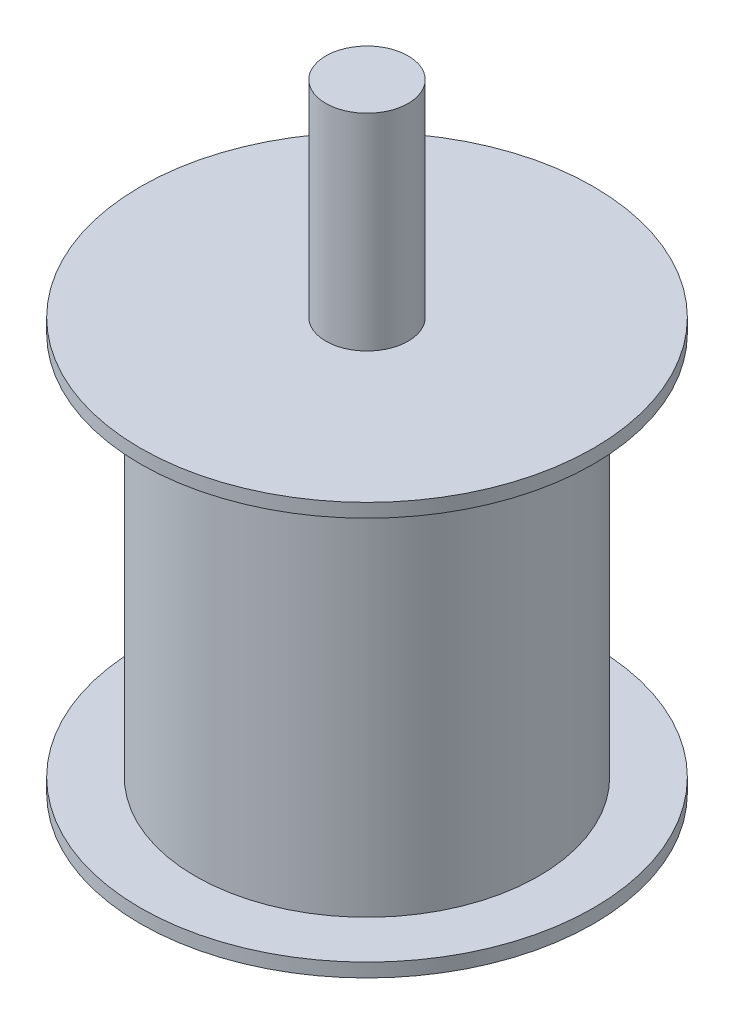
SolidWorks part; units mm, degrees
ref_plane "Plan de face" through (0, 0, 0) normal (0, 0, 1) x (1, 0, 0)
ref_plane "Plan de dessus" through (0, 0, 0) normal (0, 1, 0) x (1, 0, 0)
ref_plane "Plan de droite" through (0, 0, 0) normal (1, 0, 0) x (0, 0, -1)
sketch "Esquisse1" plane through (0, 0, 0) normal (0, 1, 0) x (1, 0, 0)
  circle A0 centre (0, 0) radius 16.5
  circle A1 centre (0, 0) radius 12.5
  dimension "D1" = 4
  dimension "D2" = 25
extrude "Boss.-Extru.1" add sketch "Esquisse1" along normal blind 30 contours A1 region at (0, 0, 0)
extrude "Boss.-Extru.2" add sketch "Esquisse1<3>" along normal blind 1
sketch "Esquisse1<3>" plane through (0, 0, 0) normal (0, 1, 0) x (1, 0, 0) same geometry as "Esquisse1"
sketch "Esquisse2" plane through (0, 30, 0) normal (0, 1, 0) x (1, 0, 0)
  circle A0 centre (0, 0) radius 16.5
  circle A1 centre (0, 0) radius 16.5 construction
extrude "Boss.-Extru.3" add sketch "Esquisse2" against normal blind 1
sketch "Esquisse3" plane through (0, 0, 0) normal (0, -1, 0) x (1, 0, 0)
  circle A0 centre (0, 0) radius 1.1525
  dimension "D1" = 2.305
sketch "Esquisse4" plane through (0, 30, 0) normal (0, 1, 0) x (1, 0, 0)
  circle A0 centre (0, 0) radius 3
  dimension "D1" = 6
extrude "Enlèv. mat.-Extru.1" cut sketch "Esquisse3" against normal blind 6 contours A0
extrude "Boss.-Extru.4" add sketch "Esquisse4" along normal blind 15 contours A0
sketch3d "Esquisse3D1"
  line L0 (0, 0, 0) -> (0, 14.0713, 0) construction
  line L1 (0, 14.0713, 0) -> (0, 28.1427, 0) construction
  line L2 (0, 45, 0) -> (0, 30, 0) construction
  line L3 (0, 29, 0) -> (0, 30, 0) construction
